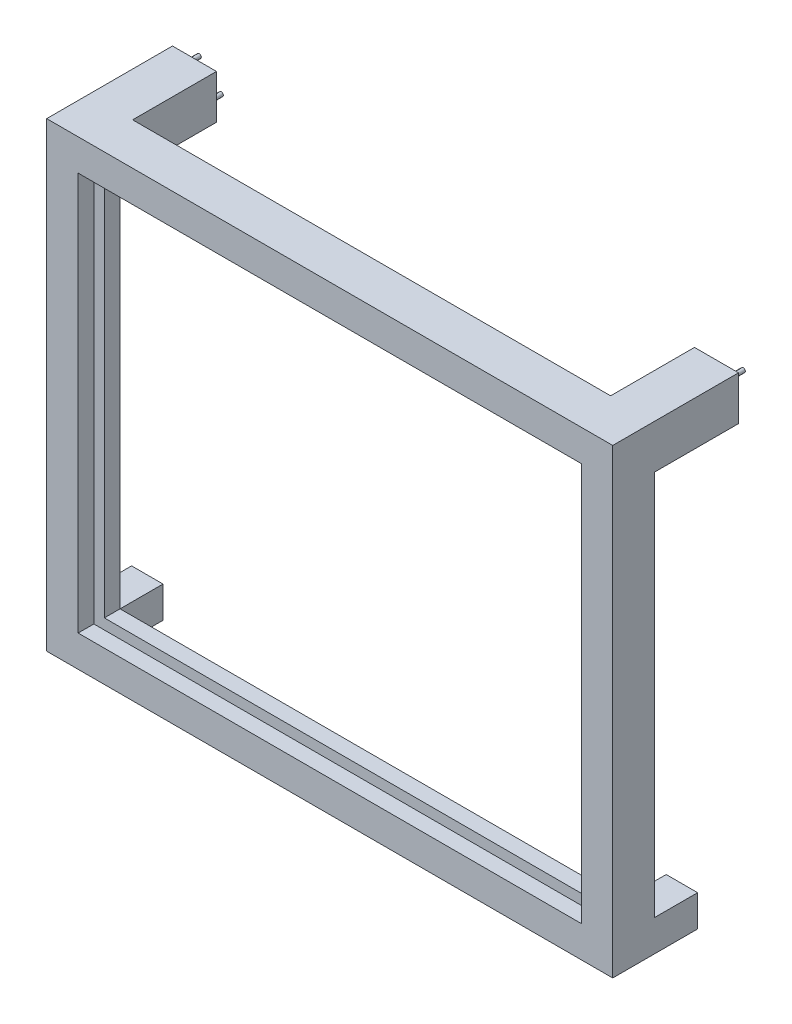
SolidWorks part; units mm, degrees
ref_plane "Plan de face" through (0, 0, 0) normal (0, 0, 1) x (1, 0, 0)
ref_plane "Plan de dessus" through (0, 0, 0) normal (0, 1, 0) x (1, 0, 0)
ref_plane "Plan de droite" through (0, 0, 0) normal (1, 0, 0) x (0, 0, -1)
sketch "Esquisse1" plane through (0, 0, 0) normal (0, 0, 1) x (1, 0, 0)
  line L1 (-240, -190) -> (240, -190)
  line L2 (-240, -190) -> (-240, 190)
  line L3 (-240, 190) -> (240, 190)
  line L4 (240, -190) -> (240, 190)
  line L5 (-240, -190) -> (240, 190) construction
  line L6 (-240, 190) -> (240, -190) construction
  line L7 (-270, -220) -> (270, -220)
  line L8 (-270, -220) -> (-270, 220)
  line L9 (-270, 220) -> (270, 220)
  line L10 (270, -220) -> (270, 220)
  line L11 (-270, -220) -> (270, 220) construction
  line L12 (-270, 220) -> (270, -220) construction
  point P0 (0, 0)
  point P6 (0, 0)
  dimension "D1" = 540
  dimension "D2" = 440
  dimension "D3" = 480
  dimension "D4" = 380
extrude "Boss.-Extru.1" add sketch "Esquisse1" along normal blind 40
sketch "Esquisse2" plane through (0, -190, 0) normal (0, 1, 0) x (1, 0, 0)
  line L0 (-240, -40) -> (240, -40) construction
  line L1 (-250, -25) -> (250, -25)
  line L2 (-250, -25) -> (-250, -15)
  line L3 (-250, -15) -> (250, -15)
  line L4 (250, -25) -> (250, -15)
  line L5 (270, 0) -> (-270, 0) construction
  line L6 (-270, -40) -> (-270, 0) construction
  line L7 (270, -40) -> (270, 0) construction
  dimension "D1" = 15
  dimension "D2" = 15
  dimension "D3" = 20
  dimension "D4" = 20
extrude "Enlèv. mat.-Extru.1" cut sketch "Esquisse2" along normal blind 390 and the other way blind 10
sketch "Esquisse3" plane through (0, 0, 0) normal (0, 0, -1) x (-1, 0, 0)
  line L0 (-270, -220) -> (-270, 220) construction
  line L9 (-270, 220) -> (-228, 220)
  line L10 (-270, 220) -> (-270, 178)
  line L11 (-270, 178) -> (-228, 178)
  line L12 (-228, 220) -> (-228, 178)
  line L13 (-270, 220) -> (270, 220) construction
  line L15 (270, 220) -> (228, 220)
  line L16 (270, 220) -> (270, 178)
  line L17 (270, 178) -> (228, 178)
  line L18 (228, 220) -> (228, 178)
  dimension "D1" = 42
  dimension "D2" = 42
  dimension "D3" = 42
  dimension "D4" = 42
extrude "Boss.-Extru.2" add sketch "Esquisse3" along normal blind 80
sketch "Esquisse5" plane through (0, 0, -80) normal (0, 0, -1) x (-1, 0, 0)
  line L0 (270, 220) -> (249, 199) construction
  line L1 (-270, 220) -> (-249, 199) construction
  line L2 (-249, 199) -> (-228, 178) construction
  line L3 (249, 199) -> (228, 178) construction
  circle A0 centre (-259.5, 209.5) radius 2
  circle A1 centre (-238.5, 188.5) radius 2
  circle A2 centre (259.5, 209.5) radius 2
  circle A3 centre (238.5, 188.5) radius 2
  dimension "D1" = 4
  dimension "D2" = 4
  dimension "D3" = 4
  dimension "D4" = 4
extrude "Boss.-Extru.3" add sketch "Esquisse5" along normal blind 15
sketch "Esquisse7" plane through (0, 178, 0) normal (0, -1, 0) x (1, 0, 0)
  line L0 (228, -80) -> (228, -41) construction
  line L1 (-228, -80) -> (-228, -41) construction
  line L2 (-228, -80) -> (-228, 0) construction
  line L3 (-228, -41) -> (-270, -80) construction
  line L5 (228, -80) -> (228, 0) construction
  line L6 (228, -41) -> (270, -80) construction
  circle A0 centre (249, -60.5) radius 4
  circle A1 centre (-249, -60.5) radius 4
  dimension "D1" = 8
  dimension "D2" = 8
  dimension "D3" = 39
  dimension "D4" = 39
extrude "Enlèv. mat.-Extru.2" cut sketch "Esquisse7" against normal blind 20
sketch "Esquisse8" plane through (0, 0, 0) normal (0, 0, -1) x (-1, 0, 0)
  line L1 (-270, -220) -> (-240, -220)
  line L2 (-270, -220) -> (-270, -190)
  line L3 (-270, -190) -> (-240, -190)
  line L4 (-240, -220) -> (-240, -190)
  line L5 (240, -190) -> (270, -190)
  line L6 (240, -190) -> (240, -220)
  line L7 (240, -220) -> (270, -220)
  line L8 (270, -190) -> (270, -220)
extrude "Boss.-Extru.4" add sketch "Esquisse8" along normal blind 41
